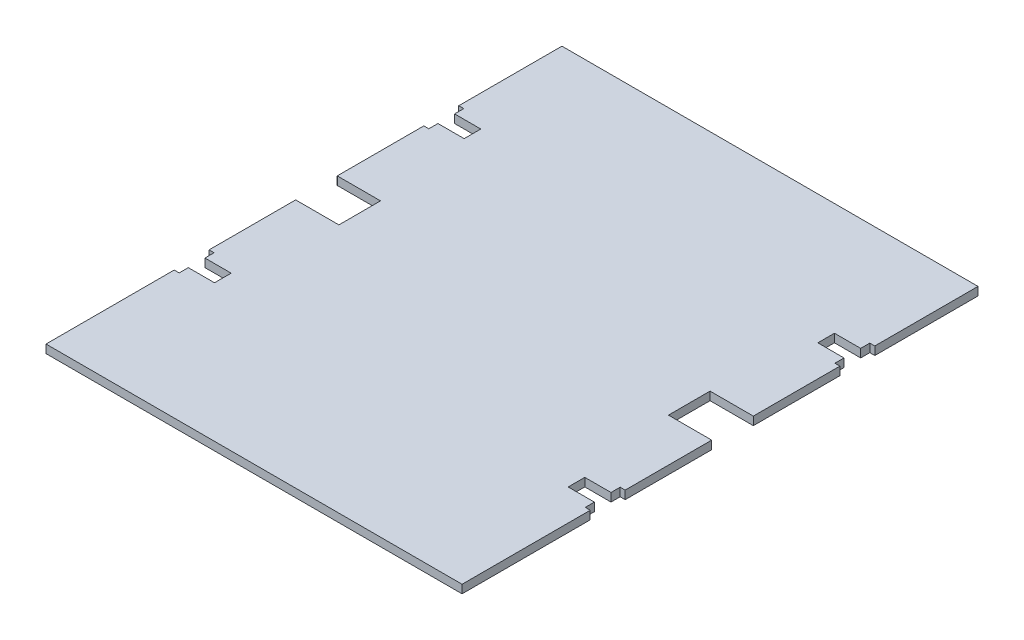
SolidWorks part; units mm, degrees
ref_plane "Front Plane" through (0, 0, 0) normal (0, 0, 1) x (1, 0, 0)
ref_plane "Top Plane" through (0, 0, 0) normal (0, 1, 0) x (1, 0, 0)
ref_plane "Right Plane" through (0, 0, 0) normal (1, 0, 0) x (0, 0, -1)
sketch "Sketch1" plane through (0, 0, 0) normal (0, 1, 0) x (1, 0, 0)
  line L1 (-250, -310) -> (250, -310)
  line L2 (-250, -310) -> (-250, 310)
  line L3 (-250, 310) -> (250, 310)
  line L4 (250, -310) -> (250, 310)
  line L5 (-250, -310) -> (250, 310) construction
  line L6 (-250, 310) -> (250, -310) construction
  point P0 (0, 0)
  dimension "D1" = 500
  dimension "D2" = 620
extrude "Boss-Extrude1" add sketch "Sketch1" along normal blind 10
sketch "Sketch2" plane through (0, 10, 0) normal (0, 1, 0) x (1, 0, 0)
  line L0 (-250, 310) -> (-250, -310) construction
  line L1 (-250, 40) -> (-198, 40)
  line L2 (-250, 40) -> (-250, -10)
  line L3 (-250, -10) -> (-198, -10)
  line L4 (-198, 40) -> (-198, -10)
  line L5 (250, -310) -> (250, 310) construction
  line L6 (250, 40) -> (198, 40)
  line L7 (250, 40) -> (250, -10)
  line L8 (250, -10) -> (198, -10)
  line L9 (198, 40) -> (198, -10)
  line L10 (250, 310) -> (-250, 310) construction
  line L11 (0, 310) -> (0, -310) construction
  line L12 (-250, 186) -> (-244, 186)
  line L13 (-250, 186) -> (-250, 144)
  line L14 (-250, 144) -> (-244, 144)
  line L15 (-244, 186) -> (-244, 175)
  line L16 (-244, 175) -> (-212.5, 175)
  line L18 (-244, 155) -> (-212.5, 155)
  line L19 (-212.5, 175) -> (-212.5, 155)
  line L20 (-250, -310) -> (250, -310) construction
  line L21 (-92.6056, 0) -> (108.2015, 0) construction
  line L22 (212.5, 175) -> (212.5, 155)
  line L23 (244, 155) -> (212.5, 155)
  line L25 (244, 175) -> (212.5, 175)
  line L26 (244, 186) -> (244, 175)
  line L27 (250, 144) -> (244, 144)
  line L28 (250, 186) -> (250, 144)
  line L29 (250, 186) -> (244, 186)
  line L46 (212.5, -125) -> (212.5, -145)
  line L47 (-250, -114) -> (-244, -114)
  line L48 (-250, -114) -> (-250, -156)
  line L49 (-250, -156) -> (-244, -156)
  line L50 (-244, -114) -> (-244, -125)
  line L51 (-244, -125) -> (-212.5, -125)
  line L53 (-244, -145) -> (-212.5, -145)
  line L54 (-212.5, -125) -> (-212.5, -145)
  line L55 (244, -145) -> (212.5, -145)
  line L57 (244, -125) -> (212.5, -125)
  line L58 (244, -114) -> (244, -125)
  line L59 (250, -156) -> (244, -156)
  line L60 (250, -114) -> (250, -156)
  line L61 (250, -114) -> (244, -114)
  line L62 (-244, 155) -> (-244, 144)
  line L63 (244, 155) -> (244, 144)
  line L64 (244, -145) -> (244, -156)
  line L65 (-244, -145) -> (-244, -156)
  dimension "D1" = 270
  dimension "D2" = 50
  dimension "D3" = 52
  dimension "D4" = 52
  dimension "D5" = 50
  dimension "D6" = 270
  dimension "D7" = 124
  dimension "D8" = 42
  dimension "D9" = 6
  dimension "D10" = 31.5
  dimension "D11" = 20
  dimension "D12" = 6
  dimension "D13" = 42
  dimension "D14" = 31.5
  dimension "D15" = 20
  dimension "D16" = 154
extrude "Cut-Extrude1" cut sketch "Sketch2" against normal blind 10
